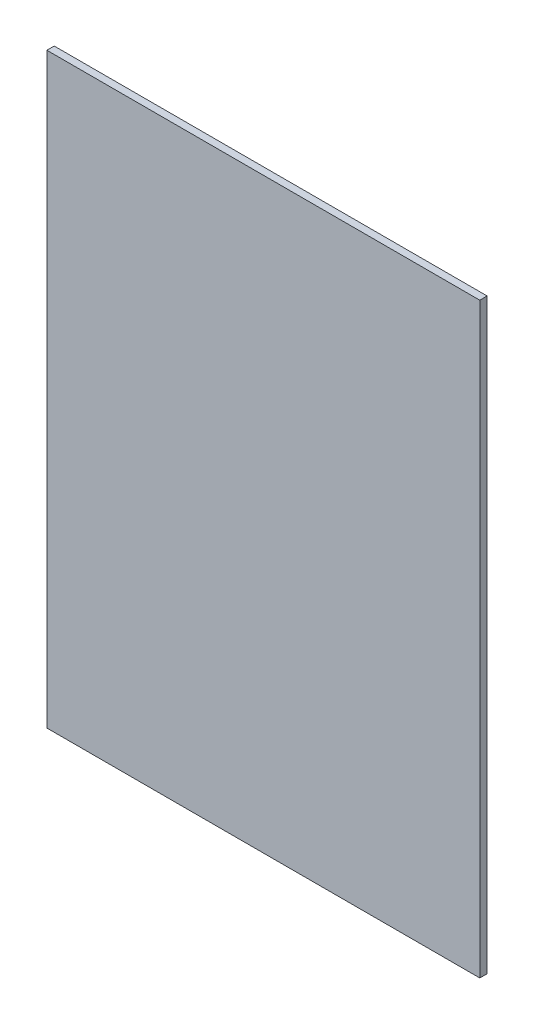
SolidWorks part; units mm, degrees
ref_plane "Front Plane" through (0, 0, 0) normal (0, 0, 1) x (1, 0, 0)
ref_plane "Top Plane" through (0, 0, 0) normal (0, 1, 0) x (1, 0, 0)
ref_plane "Right Plane" through (0, 0, 0) normal (1, 0, 0) x (0, 0, -1)
sketch "Sketch1" plane through (0, 0, 0) normal (0, 0, 1) x (1, 0, 0)
  line L1 (-93.6625, -127) -> (93.6625, -127)
  line L2 (-93.6625, -127) -> (-93.6625, 127)
  line L3 (-93.6625, 127) -> (93.6625, 127)
  line L4 (93.6625, -127) -> (93.6625, 127)
  line L5 (-93.6625, -127) -> (93.6625, 127) construction
  line L6 (-93.6625, 127) -> (93.6625, -127) construction
  point P0 (0, 0)
  dimension "D1" = 187.325
  dimension "D2" = 254
extrude "Boss-Extrude1" add sketch "Sketch1" along normal blind 3.175
